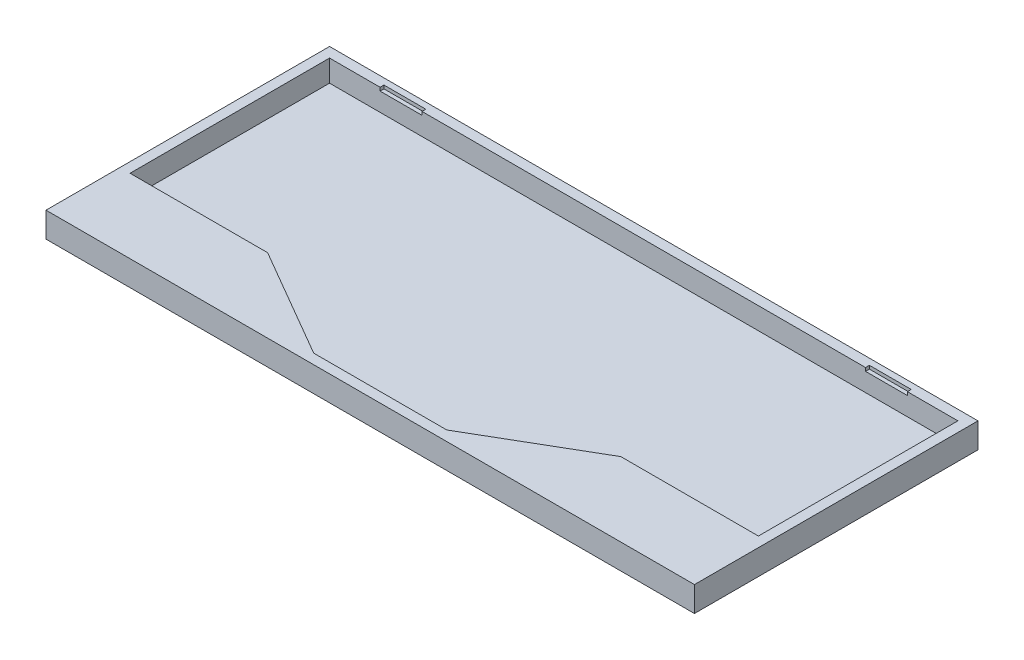
SolidWorks part; units mm, degrees
ref_plane "Front Plane" through (0, 0, 0) normal (0, 0, 1) x (1, 0, 0)
ref_plane "Top Plane" through (0, 0, 0) normal (0, 1, 0) x (1, 0, 0)
ref_plane "Right Plane" through (0, 0, 0) normal (1, 0, 0) x (0, 0, -1)
sketch "Sketch1" plane through (0, 0, 0) normal (0, 1, 0) x (1, 0, 0)
  line L1 (-193.7, 84.7) -> (193.7, 84.7)
  line L2 (-193.7, 84.7) -> (-193.7, -84.7)
  line L3 (-193.7, -84.7) -> (193.7, -84.7)
  line L4 (193.7, 84.7) -> (193.7, -84.7)
  line L5 (-193.7, 84.7) -> (193.7, -84.7) construction
  line L6 (-193.7, -84.7) -> (193.7, 84.7) construction
  point P0 (0, 0)
  dimension "D1" = 387.4
  dimension "D2" = 169.4
extrude "Boss-Extrude1" add sketch "Sketch1" along normal blind 15
sketch "Sketch2" plane through (0, 15, 0) normal (0, 1, 0) x (1, 0, 0)
  line L0 (0, 78.7) -> (0, 84.7) construction
  line L2 (-187.7, 78.7) -> (187.7, 78.7)
  line L3 (-187.7, 78.7) -> (-187.7, -78.7)
  line L4 (-187.7, -78.7) -> (187.7, -78.7)
  line L5 (187.7, 78.7) -> (187.7, -78.7)
  line L6 (-187.7, 78.7) -> (187.7, -78.7) construction
  line L7 (-187.7, -78.7) -> (187.7, 78.7) construction
  line L8 (193.7, 84.7) -> (-193.7, 84.7) construction
  line L9 (187.7, 0) -> (193.7, 0) construction
  line L10 (193.7, -84.7) -> (193.7, 84.7) construction
  point P0 (0, 0)
  dimension "D1" = 6
  dimension "D2" = 6
extrude "Cut-Extrude1" cut sketch "Sketch2" against normal offset from surface (13 mm away) 2 up to face at (0, 0, 0)
sketch "Sketch3" plane through (0, 15, 0) normal (0, 1, 0) x (1, 0, 0)
  line L0 (193.7, 84.7) -> (157.5, 84.7) construction
  line L1 (193.7, 84.7) -> (-193.7, 84.7) construction
  line L2 (157.5, 81) -> (157.5, 78.7)
  line L3 (-187.7, 78.7) -> (187.7, 78.7) construction
  line L4 (157.5, 78.7) -> (132.5, 78.7)
  line L5 (187.7, 78.7) -> (-187.7, 78.7) construction
  line L6 (132.5, 78.7) -> (132.5, 81)
  line L7 (132.5, 81) -> (157.5, 81)
  line L8 (157.5, 81) -> (157.5, 84.7) construction
  line L9 (-193.7, 84.7) -> (-157.5, 84.7) construction
  line L10 (-157.5, 81) -> (-157.5, 78.7)
  line L11 (-157.5, 78.7) -> (-132.5, 78.7)
  line L12 (-132.5, 78.7) -> (-132.5, 81)
  line L13 (-132.5, 81) -> (-157.5, 81)
  line L14 (-157.5, 81) -> (-157.5, 84.7) construction
  dimension "D1" = 36.2
  dimension "D2" = 2.3
  dimension "D3" = 25
  dimension "D4" = 36.2
  dimension "D5" = 2.3
  dimension "D6" = 25
extrude "Cut-Extrude2" cut sketch "Sketch3" against normal blind 2
sketch "Sketch4" plane through (0, 2, 0) normal (0, 1, 0) x (1, 0, 0)
  line L0 (187.7, -40.5) -> (105.5, -40.5)
  line L1 (187.7, -78.7) -> (187.7, 78.7) construction
  line L3 (105.5, -40.5) -> (39.7605, -78.7)
  line L4 (-187.7, -78.7) -> (187.7, -78.7) construction
  line L8 (-39.7605, -78.7) -> (-105.5, -40.5)
  line L9 (-105.5, -40.5) -> (-187.7, -40.5)
  line L10 (-187.7, 78.7) -> (-187.7, -78.7) construction
  line L12 (-187.7, -40.5) -> (-187.7, -78.7)
  line L13 (-187.7, -78.7) -> (-39.7605, -78.7)
  line L14 (39.7605, -78.7) -> (187.7, -78.7)
  line L15 (187.7, -78.7) -> (187.7, -40.5)
  point P10 (0, 0)
  point P11 (0, 0)
  point P25 (0, 0)
  dimension "D1" = 38.2
  dimension "D2" = 82.2
  dimension "D3" = 147.9395
extrude "Boss-Extrude2" add sketch "Sketch4" along normal up to surface (13 mm away) up to face at (0, 15, -53.2333)
equation "\"full_width\"=375"
equation "\"D1@Sketch1\"=\"full_width\"+(\"added_width\"*2)+(\"margin1\"*2)"
equation "\"added_width\"=6"
equation "\"full_height\"= 157"
equation "\"D2@Sketch1\"=\"full_height\"+(\"added_height\"*2)+(\"margin1\"*2)"
equation "\"added_height\"=6"
equation "\"D1@Sketch3\"=30.00mm+\"added_width\"+\"margin1\""
equation "\"tab_depth\"=2.5"
equation "\"D2@Sketch3\"=\"tab_depth\"-\"margin1\""
equation "\"tab_width\"=25"
equation "\"D3@Sketch3\"=\"tab_width\""
equation "\"tab_height\"=2"
equation "\"D1@Cut-Extrude2\"=\"tab_height\""
equation "\"D4@Sketch3\"=30mm+\"added_width\"+\"margin1\""
equation "\"D5@Sketch3\"=\"tab_depth\"-\"margin1\""
equation "\"D6@Sketch3\"=\"tab_width\""
equation "\"D2@Sketch2\"=\"added_height\""
equation "\"D1@Sketch2\"=\"added_width\""
equation "\"margin1\"= 0.2"
